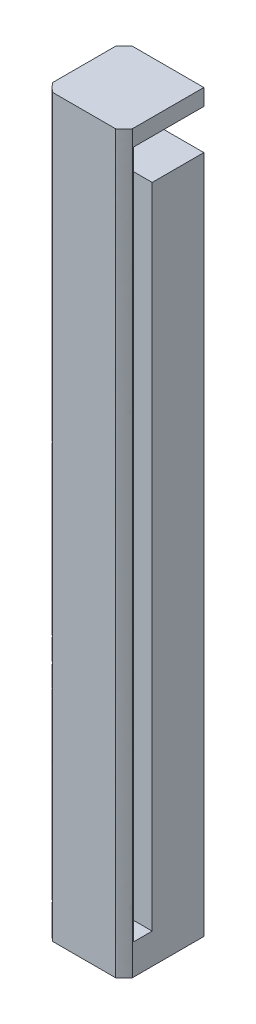
SolidWorks part; units mm, degrees
ref_plane "Front Plane" through (0, 0, 0) normal (0, 0, 1) x (1, 0, 0)
ref_plane "Top Plane" through (0, 0, 0) normal (0, 1, 0) x (1, 0, 0)
ref_plane "Right Plane" through (0, 0, 0) normal (1, 0, 0) x (0, 0, -1)
sketch "Sketch1" plane through (0, 0, 0) normal (0, 1, 0) x (1, 0, 0)
  line L1 (0, 0) -> (10, 0)
  line L2 (0, 0) -> (0, 10)
  line L3 (0, 10) -> (10, 10)
  line L4 (10, 0) -> (10, 10)
  dimension "D1" = 10
extrude "Boss-Extrude1" add sketch "Sketch1" along normal blind 75
sketch "Sketch3" plane through (0, 0, -10) normal (0, 0, -1) x (-1, 0, 0)
  line L0 (-10, 75) -> (-10, 0) construction
  line L1 (-2.5, 73.25) -> (-10, 73.25)
  line L2 (-2.5, 73.25) -> (-2.5, 69)
  line L3 (-2.5, 69) -> (-10, 69)
  line L4 (-10, 73.25) -> (-10, 69)
  line L5 (-10, 75) -> (0, 75) construction
  line L6 (0, 75) -> (0, 0) construction
  dimension "D1" = 1.75
  dimension "D2" = 4.25
  dimension "D3" = 2.5
extrude "Cut-Extrude1" cut sketch "Sketch3" against normal offset from surface (7.5 mm away) 2.5 up to face at (5, 37.5, 0)
sketch "Sketch4" plane through (0, 0, 0) normal (0, -1, 0) x (1, 0, 0)
  line L0 (2.5, -2.5) -> (2.5, -10) construction
  line L1 (2.5, -2.5) -> (2.5, -10)
  line L2 (2.5, -2.5) -> (10, -2.5) construction
  line L3 (2.5, -2.5) -> (10, -2.5)
  line L4 (10, -10) -> (0, -10) construction
  line L5 (10, -2.5) -> (2.5, -2.5)
  line L6 (10, -2.5) -> (10, -4.5)
  line L7 (10, -4.5) -> (2.5, -4.5)
  line L8 (2.5, -2.5) -> (2.5, -4.5)
  line L9 (4.5, -10) -> (2.5, -10)
  line L10 (4.5, -10) -> (4.5, -4.5)
  line L11 (4.5, -4.5) -> (2.5, -4.5)
  line L12 (2.5, -10) -> (2.5, -4.5)
  line M10 (0, -10) -> (10, -10)
  line M11 (10, -10) -> (10, 0)
  dimension "D1" = 2
  dimension "D2" = 2
extrude "Cut-Extrude2" cut sketch "Sketch4" against normal up to surface (73.25 mm away) contours L7 L3 L1 M11 | L10 L7 L1 M10 region at (6.25, 0, -3.5) region at (3.5, 0, -7.25) up to face at (6.25, 73.25, -6.25)
sketch "Sketch5" plane through (0, 0, 0) normal (0, -1, 0) x (1, 0, 0)
  line L1 (0, 0) -> (10, 0)
  line L2 (0, 0) -> (0, -10)
  line L3 (0, -10) -> (10, -10)
  line L4 (10, 0) -> (10, -10)
extrude "Boss-Extrude2" add sketch "Sketch5" along normal blind 3.25
sketch "Sketch6" plane through (0, 0, 0) normal (0, 1, 0) x (1, 0, 0)
  line L0 (10, 4.5) -> (4.5, 4.5) construction
  line L1 (2.5, 2.5) -> (6.4, 2.5)
  line L2 (2.5, 2.5) -> (2.5, 4.5)
  line L3 (2.5, 4.5) -> (6.4, 4.5)
  line L4 (6.4, 2.5) -> (6.4, 4.5)
  line L5 (4.5, 10) -> (4.5, 4.5) construction
  line L6 (2.5, 4.5) -> (4.5, 4.5)
  line L7 (2.5, 4.5) -> (2.5, 6.4)
  line L8 (2.5, 6.4) -> (4.5, 6.4)
  line L9 (4.5, 4.5) -> (4.5, 6.4)
  line L10 (3.5, 2.5) -> (3.5, 6.4) construction
  line M7 (10, 4.5) -> (4.5, 4.5)
  line M8 (4.5, 4.5) -> (4.5, 10)
  line M10 (2.5, 10) -> (2.5, 2.5)
  line M11 (2.5, 2.5) -> (10, 2.5)
  dimension "D1" = 3.9
extrude "Boss-Extrude3" add sketch "Sketch6" along normal up to surface (73.25 mm away) contours L10 L1 L4 L6 M7 | L10 L6 L8 M8 | L3 L10 L8 M10 | L10 L3 M11 M10 region at (3, 0, -3.5) region at (4.95, 0, -3.5) region at (3, 0, -5.45) region at (4, 0, -5.45) up to face at (6.25, 73.25, -6.25)
sketch "Sketch7" plane through (0, -3.25, 0) normal (0, -1, 0) x (1, 0, 0)
  line L0 (5, 0) -> (5, -10) construction
  line L1 (10, 0) -> (0, 0) construction
  line L2 (0, -10) -> (10, -10) construction
  circle A0 centre (5, -5) radius 2.175
  dimension "D1" = 4.35
extrude "Cut-Extrude3" cut sketch "Sketch7" against normal blind 3
sketch "Sketch8" plane through (0, 75, 0) normal (0, 1, 0) x (1, 0, 0)
  line L0 (0, 0) -> (10, 0) construction
  line L1 (0, 10) -> (1.5, 10)
  line L2 (0, 10) -> (0, 0)
  line L3 (0, 0) -> (1.5, 0)
  line L4 (1.5, 10) -> (1.5, 0)
  line L5 (10, 0) -> (10, 10) construction
  line L6 (10, 1.5) -> (1.5, 1.5)
  line L7 (10, 1.5) -> (10, 0)
  line L8 (10, 0) -> (1.5, 0)
  line L9 (1.5, 1.5) -> (1.5, 0)
  line L10 (10, 2.5) -> (10, 10) construction
  line L11 (10, 2.5) -> (10, 10)
  line M3 (0, 10) -> (0, 0)
  line M4 (0, 0) -> (10, 0)
  line M5 (10, 0) -> (10, 10)
  line M6 (10, 10) -> (0, 10)
  dimension "D1" = 1
extrude "Cut-Extrude4" cut sketch "Sketch8" against normal through all contours L4 M6 M3 M4 | L6 L4 M5 M4 region at (0.75, 75, -5) region at (5.75, 75, -0.75)
fillet "Fillet1" radius 0.9 3 edges at (10, 35.875, -1.5) (1.5, 35.875, -1.5) (1.5, 35.875, -10) conic rho 0.05
